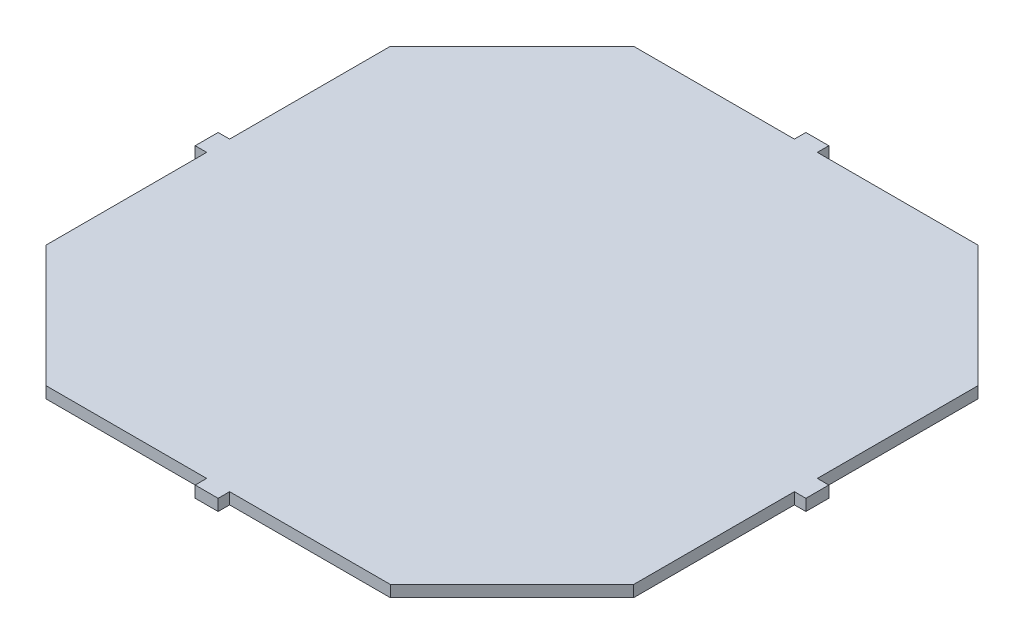
SolidWorks part; units mm, degrees
material "Acrylic (Medium-high impact)"
ref_plane "Front Plane" through (0, 0, 0) normal (0, 0, 1) x (1, 0, 0)
ref_plane "Top Plane" through (0, 0, 0) normal (0, 1, 0) x (1, 0, 0)
ref_plane "Right Plane" through (0, 0, 0) normal (1, 0, 0) x (0, 0, -1)
sketch "Sketch1" plane through (0, 0, 0) normal (0, 1, 0) x (1, 0, 0)
  line L0 (-25.6066, 15) -> (-15, 25.6066)
  line L1 (-15, -25.6066) -> (15, -25.6066)
  line L2 (-25.6066, -15) -> (-25.6066, 15)
  line L3 (-15, 25.6066) -> (15, 25.6066)
  line L4 (25.6066, -15) -> (25.6066, 15)
  line L5 (-20.3033, -20.3033) -> (20.3033, 20.3033) construction
  line L6 (-20.3033, 20.3033) -> (20.3033, -20.3033) construction
  line L7 (-25.6066, -15) -> (-15, -25.6066)
  line L8 (15, -25.6066) -> (25.6066, -15)
  line L9 (15, 25.6066) -> (25.6066, 15)
  point P0 (0, 0)
  dimension "D1" = 30
  dimension "D2" = 30
  dimension "D3" = 135
  dimension "D4" = 135
  dimension "D5" = 15
  dimension "D6" = 135
extrude "Boss-Extrude1" add sketch "Sketch1" along normal blind 1
sketch "Sketch2" plane through (0, 1, 0) normal (0, 1, 0) x (1, 0, 0)
  line L0 (0, 25.6066) -> (0, -25.6066) construction
  line L1 (15, 25.6066) -> (-15, 25.6066) construction
  line L2 (-15, -25.6066) -> (15, -25.6066) construction
  line L3 (-25.6066, 0) -> (25.6066, 0) construction
  line L4 (-25.6066, 15) -> (-25.6066, -15) construction
  line L5 (25.6066, -15) -> (25.6066, 15) construction
  line L6 (-25.6066, 1) -> (-26.6066, 1)
  line L7 (-26.6066, 1) -> (-26.6066, -1)
  line L8 (-26.6066, -1) -> (-25.6066, -1)
  line L9 (-1, 25.6066) -> (-1, 26.6066)
  line L10 (-1, 26.6066) -> (1, 26.6066)
  line L11 (1, 26.6066) -> (1, 25.6066)
  line L12 (1, -26.6066) -> (1, -25.6066)
  line L13 (-1, -26.6066) -> (1, -26.6066)
  line L14 (-1, -25.6066) -> (-1, -26.6066)
  line L15 (26.6066, -1) -> (25.6066, -1)
  line L16 (26.6066, 1) -> (26.6066, -1)
  line L17 (25.6066, 1) -> (26.6066, 1)
  line L18 (-1, 25.6066) -> (1, 25.6066)
  line L19 (25.6066, 1) -> (25.6066, -1)
  line L20 (-1, -25.6066) -> (1, -25.6066)
  line L21 (-25.6066, -1) -> (-25.6066, 1)
  dimension "D1" = 2
  dimension "D2" = 1
  dimension "D3" = 2
  dimension "D4" = 1
extrude "Boss-Extrude2" add sketch "Sketch2" against normal blind 1
